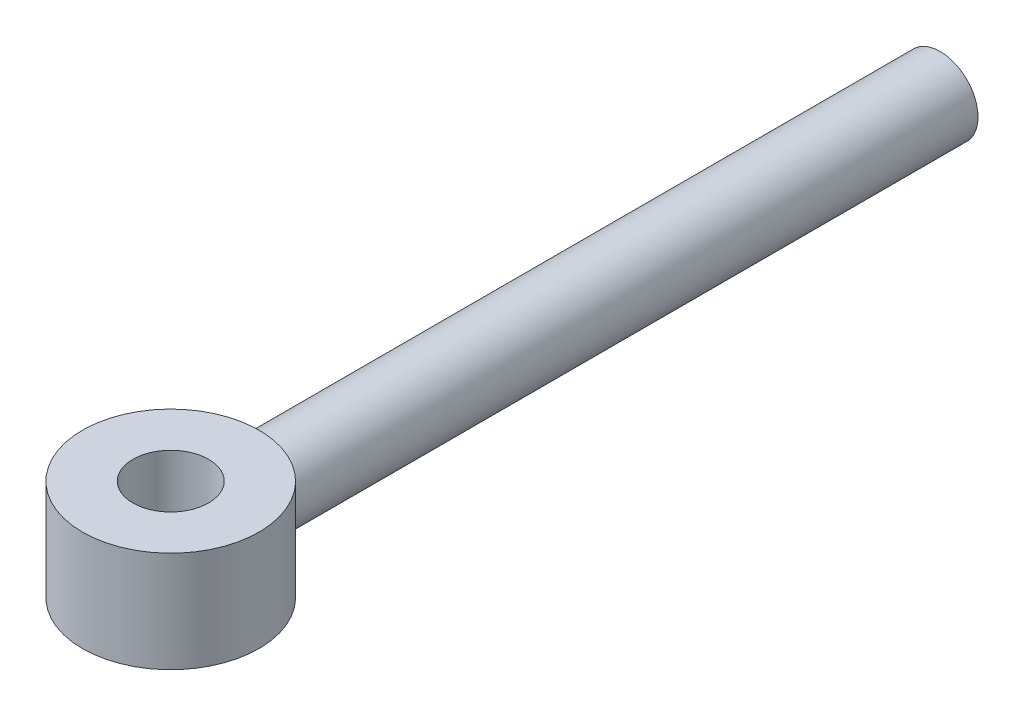
SolidWorks part; units mm, degrees
ref_plane "Спереди" through (0, 0, 0) normal (0, 0, 1) x (1, 0, 0)
ref_plane "Сверху" through (0, 0, 0) normal (0, 1, 0) x (1, 0, 0)
ref_plane "Справа" through (0, 0, 0) normal (1, 0, 0) x (0, 0, -1)
sketch "Эскиз1" plane through (0, 0, 0) normal (0, 0, 1) x (1, 0, 0)
  circle A0 centre (0, 0) radius 3
  dimension "D1" = 6
extrude "Бобышка-Вытянуть1" add sketch "Эскиз1" along normal blind 55
sketch "Эскиз3" plane through (0, 0, 0) normal (0, 1, 0) x (1, 0, 0)
  line L0 (-3, -55) -> (3, -55) construction
  circle A0 centre (0, -61) radius 7
  dimension "D2" = 14
  dimension "D1" = 6
extrude "Бобышка-Вытянуть2" add sketch "Эскиз3" along normal blind 4 and the other way blind 4
sketch "Эскиз4" plane through (0, 4, 0) normal (0, 1, 0) x (1, 0, 0)
  circle A0 centre (0, -61) radius 3
  dimension "D1" = 6
extrude "Вырез-Вытянуть1" cut sketch "Эскиз4" against normal through all
